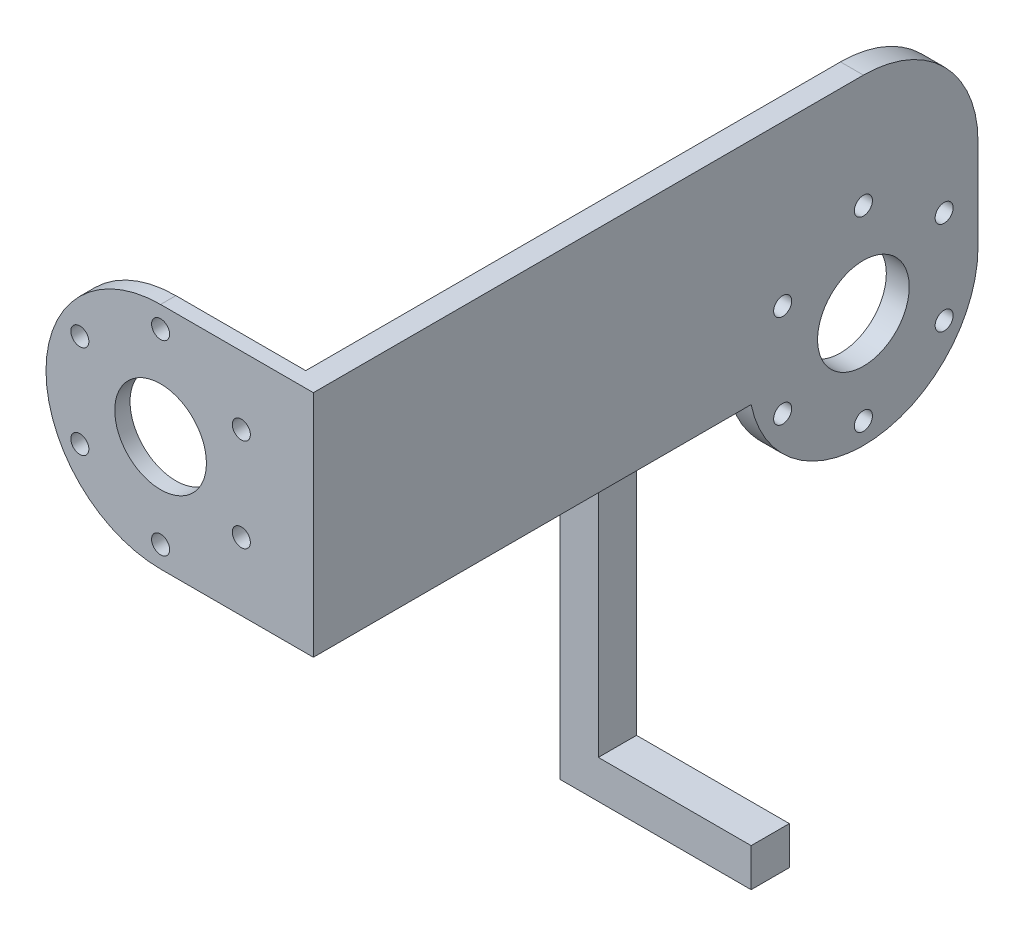
SolidWorks part; units mm, degrees
ref_plane "Front Plane" through (0, 0, 0) normal (0, 0, 1) x (1, 0, 0)
ref_plane "Top Plane" through (0, 0, 0) normal (0, 1, 0) x (1, 0, 0)
ref_plane "Right Plane" through (0, 0, 0) normal (1, 0, 0) x (0, 0, -1)
sketch "Sketch1" plane through (0, 0, 0) normal (0, 0, 1) x (1, 0, 0)
  line L1 (-25.4, -19.05) -> (25.4, -19.05)
  line L2 (-25.4, -19.05) -> (-25.4, 19.05)
  line L3 (-25.4, 19.05) -> (25.4, 19.05)
  line L4 (25.4, -19.05) -> (25.4, 19.05)
  line L5 (-25.4, -19.05) -> (25.4, 19.05) construction
  line L6 (-25.4, 19.05) -> (25.4, -19.05) construction
  circle A0 centre (0, 0) radius 15.5 construction
  circle A1 centre (0, 15.5) radius 1.5
  circle A2 centre (13.4234, 7.75) radius 1.5
  circle A3 centre (13.4234, -7.75) radius 1.5
  circle A4 centre (0, -15.5) radius 1.5
  circle A5 centre (-13.4234, -7.75) radius 1.5
  circle A6 centre (-13.4234, 7.75) radius 1.5
  circle A7 centre (0, 0) radius 7.62
  point P0 (0, 0)
  point P22 (0, 0)
  dimension "D2" = 31
  dimension "D3" = 3
  dimension "D5" = 15.24
  dimension "D1" = 38.1
  dimension "D6" = 50.8
  dimension "D4" = 6
extrude "Boss-Extrude1" add sketch "Sketch1" along normal blind 2.54
sketch "Sketch2" plane through (0, 0, 2.54) normal (0, 0, 1) x (1, 0, 0)
  line L0 (25.4, 19.05) -> (-25.4, 19.05) construction
  line L1 (-25.4, -19.05) -> (25.4, -19.05) construction
  line L2 (0, 19.05) -> (-25.4, 19.05)
  line L3 (-25.4, 19.05) -> (-25.4, -19.05)
  line L4 (-25.4, 19.05) -> (-25.4, -19.05) construction
  line L5 (-25.4, -19.05) -> (0, -19.05)
  arc A0 (0, 19.05) -> (0, -19.05) centre (0, 0) ccw
extrude "Cut-Extrude1" cut sketch "Sketch2" against normal up to next
sketch "Sketch4" plane through (25.4, 0, 0) normal (1, 0, 0) x (0, 0, -1)
  line L0 (-2.54, -19.05) -> (0, -19.05) construction
  line L1 (-2.54, 19.05) -> (88.9, 19.05)
  line L2 (-2.54, 19.05) -> (-2.54, -19.05)
  line L3 (-2.54, -19.05) -> (88.9, -19.05)
  line L4 (88.9, 19.05) -> (88.9, -19.05)
  line L5 (0, -19.05) -> (0, 19.05) construction
  line L7 (107.95, 0) -> (69.85, 0)
  line L8 (107.95, 0) -> (107.95, -15.24)
  line L9 (107.95, -15.24) -> (69.85, -15.24)
  line L10 (69.85, 0) -> (69.85, -15.24)
  circle A0 centre (88.9, 0) radius 19.05
  circle A1 centre (88.9, -15.24) radius 19.05
  point P17 (107.95, 0)
  dimension "D1" = 88.9
  dimension "D2" = 15.24
extrude "Boss-Extrude2" add sketch "Sketch4" against normal blind 3.81 contours L2 L1 L4 L3 | A0 | L8 L7 L10 L9 | A1
sketch "Sketch5" plane through (25.4, 0, 0) normal (1, 0, 0) x (0, 0, -1)
  circle A0 centre (88.9, -15.24) radius 7.62
  circle A2 centre (88.9, -15.24) radius 15.5 construction
  circle A3 centre (88.9, 0.26) radius 1.5
  circle A4 centre (102.3234, -7.49) radius 1.5
  circle A5 centre (102.3234, -22.99) radius 1.5
  circle A6 centre (88.9, -30.74) radius 1.5
  circle A7 centre (75.4766, -22.99) radius 1.5
  circle A8 centre (75.4766, -7.49) radius 1.5
  arc A9 (70.2349, -19.05) -> (107.95, -15.24) centre (88.9, -15.24) ccw construction
  dimension "D1" = 15.24
  dimension "D2" = 31
  dimension "D3" = 3
  dimension "D4" = 6
extrude "Cut-Extrude2" cut sketch "Sketch5" against normal up to next
sketch "Sketch6" plane through (0, -19.05, 0) normal (0, -1, 0) x (1, 0, 0)
  line L0 (25.4, 2.54) -> (25.4, -70.2349) construction
  line L1 (25.4, -57.5349) -> (6.35, -57.5349)
  line L2 (25.4, -57.5349) -> (25.4, -63.8849)
  line L3 (25.4, -63.8849) -> (6.35, -63.8849)
  line L4 (6.35, -57.5349) -> (6.35, -63.8849)
  line L5 (25.4, -70.2349) -> (21.59, -70.2349) construction
  dimension "D1" = 6.35
  dimension "D2" = 19.05
  dimension "D3" = 6.35
extrude "Boss-Extrude3" add sketch "Sketch6" against normal blind 6.35
sketch "Sketch7" plane through (0, -19.05, 0) normal (0, -1, 0) x (1, 0, 0)
  line L0 (6.35, -63.8849) -> (21.59, -63.8849) construction
  line L1 (6.35, -57.5349) -> (12.7, -57.5349)
  line L2 (6.35, -57.5349) -> (6.35, -63.8849)
  line L3 (6.35, -63.8849) -> (12.7, -63.8849)
  line L4 (12.7, -57.5349) -> (12.7, -63.8849)
  dimension "D1" = 6.35
extrude "Boss-Extrude4" add sketch "Sketch7" along normal blind 57.15
sketch "Sketch8" plane through (12.7, 0, 0) normal (1, 0, 0) x (0, 0, -1)
  line L0 (63.8849, -76.2) -> (63.8849, -19.05) construction
  line L1 (57.5349, -76.2) -> (63.8849, -76.2)
  line L2 (57.5349, -76.2) -> (57.5349, -69.85)
  line L3 (57.5349, -69.85) -> (63.8849, -69.85)
  line L4 (63.8849, -76.2) -> (63.8849, -69.85)
  dimension "D1" = 6.35
extrude "Boss-Extrude5" add sketch "Sketch8" along normal blind 25.4
